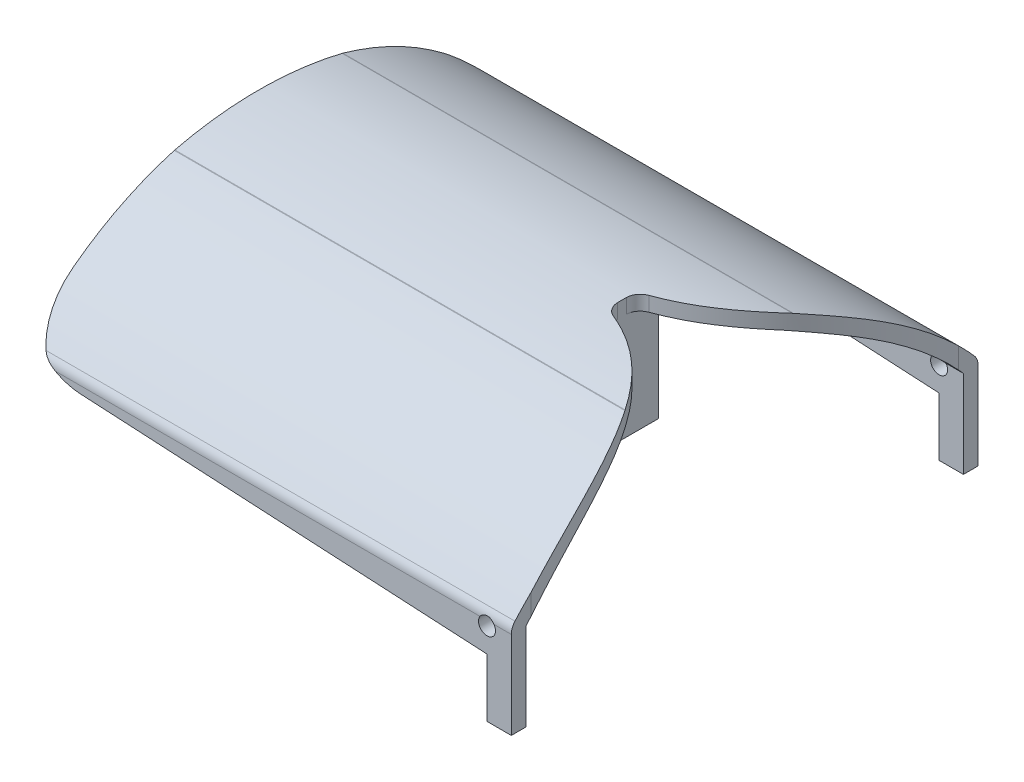
SolidWorks part; units mm, degrees
ref_plane "Front Plane" through (0, 0, 0) normal (0, 0, 1) x (1, 0, 0)
ref_plane "Top Plane" through (0, 0, 0) normal (0, 1, 0) x (1, 0, 0)
ref_plane "Right Plane" through (0, 0, 0) normal (1, 0, 0) x (0, 0, -1)
sketch "Sketch1" plane through (0, 0, 0) normal (1, 0, 0) x (0, 0, -1)
  line L1 (-45, -18) -> (-45, -32)
  line L2 (45, -18) -> (45, -32)
  arc A0 (-16.5013, 0) -> (-45, -18) centre (0, -57.6863) ccw
  arc A1 (16.5013, 0) -> (45, -18) centre (0, -57.6863) cw
  arc A2 (-16.5013, 0) -> (16.5013, 0) centre (0, -68.0272) cw
  dimension "D4" = 60
  dimension "D5" = 60
  dimension "D3" = 70
  dimension "D1" = 90
  dimension "D2" = 14
  dimension "D6" = 33.0027
  dimension "D7" = 28.4987
extrude "Extrude-Thin1" add sketch "Sketch1" along normal blind 100 thin thin type one direction wall 3
sketch "Sketch5" plane through (0, 0, 0) normal (0, 1, 0) x (1, 0, 0)
  line L0 (100, 17.2677) -> (100, 48) construction
  line L2 (74.7808, 3) -> (74.7808, -3)
  line L3 (-20.335, 0) -> (20.335, 0) construction
  line L4 (100, 44) -> (100, -44)
  spline S0 degree 2 poles (74.7808, 3) (97.6341, 10.563) (100, 44) knots 0 0 0 1 1 1
  spline S1 degree 2 poles (74.7808, -3) (97.6341, -10.563) (100, -44) knots 0 0 0 1 1 1
  point P4 (74.7808, 0)
  dimension "D1" = 3
extrude "Cut-Extrude2" cut sketch "Sketch5" against normal mid plane 67
fillet "Fillet1" radius 3 6 edges at (50, -16.8819, -48) (50, -16.8819, 48) (74.7808, 3.4098, 3) (74.7808, 3.4098, -3) (46.3282, 2.9011, -17.2677) (46.3282, 2.9011, 17.2677)
sketch "Sketch6" plane through (0, 0, -48) normal (0, 0, -1) x (-1, 0, 0)
  line L1 (-95, -24) -> (13.6709, -24)
  line L2 (-95, -24) -> (-95, -41.8798)
  line L3 (-95, -41.8798) -> (13.6709, -41.8798)
  line L4 (13.6709, -24) -> (13.6709, -41.8798)
  line L6 (-100, -32) -> (0, -32) construction
  line L7 (-100, -32) -> (-100, -18) construction
  dimension "D1" = 5
  dimension "D3" = 8
extrude "Cut-Extrude3" cut sketch "Sketch6" against normal blind 166
sketch "Sketch8" plane through (0, 0, 0) normal (0, 0, 1) x (1, 0, 0)
  line L0 (0, 1.9728) -> (-2.8489, -18)
  line L1 (100, -18) -> (0, -18) construction
  line L2 (-2.8489, -18) -> (7.1511, -18)
  line L3 (7.1511, -18) -> (15, 1.9728)
  line L4 (0, -18) -> (0, -24) construction
  line L5 (15, 1.9728) -> (0, 1.9728)
  dimension "D1" = 10
  dimension "D2" = 15
  dimension "D3" = 2.8489
extrude "Boss-Extrude1" add sketch "Sketch8" along normal mid plane 20 contours L3 L5 L0 L2
sketch "Sketch10" plane through (0, 0, 10) normal (0, 0, 1) x (1, 0, 0)
  line L0 (-2.8489, -18) -> (7.1511, -18) construction
  line L2 (-0.3489, -18) -> (3.9872, -18)
  arc A0 (-0.3489, -18) -> (3.9872, -18) centre (1.8191, -16.7552) cw
  dimension "D1" = 2.5
  dimension "D2" = 2.5
extrude "Cut-Extrude4" cut sketch "Sketch10" against normal blind 27 contours A0 L2
sketch "Sketch11" plane through (0, 0, -48) normal (0, 0, -1) x (-1, 0, 0)
  line L1 (0, -24) -> (-95, -24) construction
  line L2 (-100, -32) -> (-100, -18) construction
  circle A0 centre (-95, -19) radius 1.75
  dimension "D1" = 3.5
  dimension "D2" = 5
  dimension "D3" = 5
extrude "Cut-Extrude5" cut sketch "Sketch11" against normal blind 5
mirror "Mirror1" about plane through (0, 0, 0) normal (0, 0, 1) of "Cut-Extrude5"
sketch "Sketch12" plane through (0, 0, 0) normal (0, 0, 1) x (1, 0, 0)
  line L0 (74.7808, 1.9728) -> (74.7808, -19.91)
  line L3 (74.7808, -19.91) -> (63.1187, -19.91)
  line L4 (63.1187, -19.91) -> (63.1187, 1.9728)
  line L5 (74.7808, 1.9728) -> (15, 1.9728) construction
  line L6 (63.1187, 1.9728) -> (74.7808, 1.9728)
  point P3 (74.7808, -19.91)
  point P4 (74.7808, -19.0508)
extrude "Boss-Extrude2" add sketch "Sketch12" along normal mid plane 15
sketch "Sketch15" plane through (0, 0, -48) normal (0, 0, -1) x (-1, 0, 0)
  line L0 (-95, -24) -> (0, -18.8601)
  line L1 (0, 20.5226) -> (0, -20.5226) construction
  line L2 (0, -18.8601) -> (0, -26.572)
  line L3 (0, -26.572) -> (-95, -24)
extrude "Cut-Extrude7" cut sketch "Sketch15" against normal blind 5
mirror "Mirror2" about plane through (0, 0, 0) normal (0, 0, 1) of "Cut-Extrude7"
fillet "Fillet5" radius 12 2 edges at (0, -18.8601, 46.5) (0, -18.8601, -46.5)
sketch "Sketch16" plane through (0, -32, 0) normal (0, -1, 0) x (1, 0, 0)
  line L4 (95, -45) -> (95, -48)
  line L5 (95, -48) -> (100, -48)
  line L6 (100, -48) -> (100, -45)
  line L7 (100, -45) -> (95, -45)
  line L8 (95, -45) -> (95, -48)
  line L9 (95, -48) -> (100, -48)
  line L10 (100, -48) -> (100, -45)
  line L11 (100, -45) -> (95, -45)
  dimension "D1" = 0
extrude "Boss-Extrude3" add sketch "Sketch16" along normal blind 4
mirror "Mirror3" about plane through (0, 0, 0) normal (0, 0, 1) of "Boss-Extrude3"
